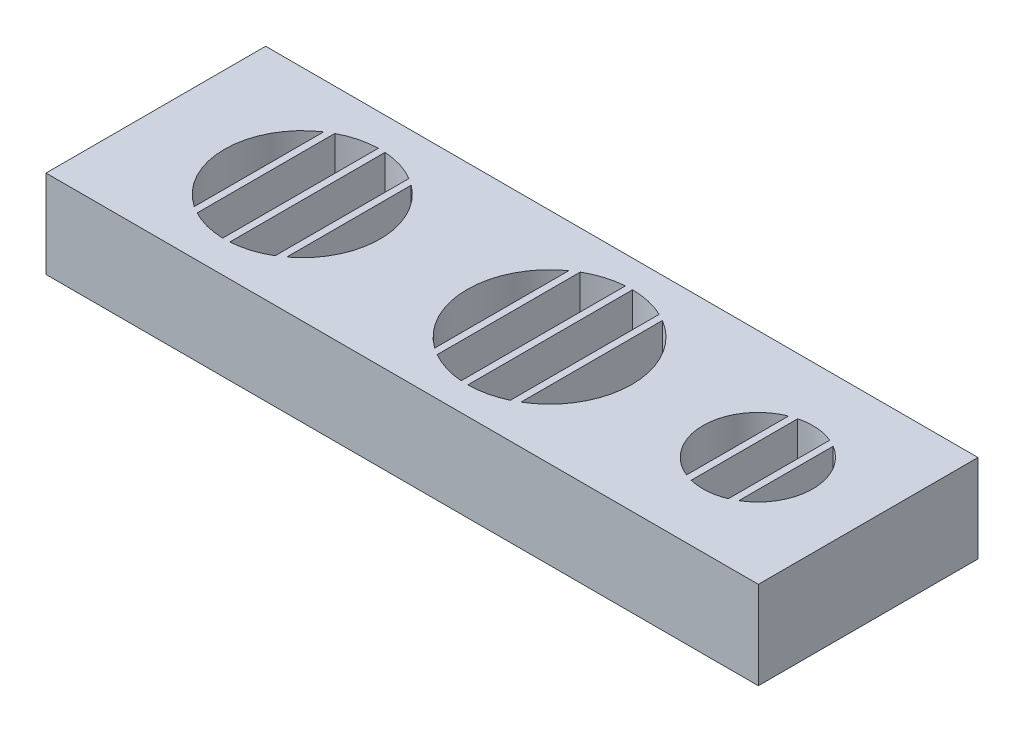
SolidWorks part; units mm, degrees
ref_plane "Front" through (0, 0, 0) normal (0, 0, 1) x (1, 0, 0)
ref_plane "Top" through (0, 0, 0) normal (0, 1, 0) x (1, 0, 0)
ref_plane "Right" through (0, 0, 0) normal (1, 0, 0) x (0, 0, -1)
sketch "Sketch1" plane through (0, 0, 0) normal (0, 1, 0) x (1, 0, 0)
  line L0 (0.8798, 6.35) -> (2.8798, 6.35)
  line L1 (0, 0) -> (38.1, 0)
  line L2 (0, 0) -> (0, 12.7)
  line L3 (0, 12.7) -> (38.1, 12.7)
  line L4 (38.1, 0) -> (38.1, 12.7)
  line L5 (2.8798, 6.35) -> (3.2798, 6.35)
  line L6 (0, 12.7) -> (-3.0858, 12.7)
  line L7 (0, 12.7) -> (0, 0)
  line L8 (0, 0) -> (-3.0858, 0)
  line L9 (-3.0858, 12.7) -> (-3.0858, 0)
  line L10 (3.2798, 6.35) -> (5.2798, 6.35)
  line L11 (5.2798, 6.35) -> (5.6798, 6.35)
  line L12 (5.6798, 6.35) -> (7.6798, 6.35)
  line L13 (7.6798, 6.35) -> (8.0798, 6.35)
  line L14 (8.0798, 6.35) -> (10.0798, 6.35)
  line L15 (2.8798, 10.0917) -> (2.8798, 2.6083)
  line L16 (3.2798, 10.3299) -> (3.2798, 2.3701)
  line L17 (5.2798, 6.35) -> (5.2798, 1.8511)
  line L18 (5.2798, 6.35) -> (5.2798, 10.8489)
  line L19 (5.6798, 6.35) -> (5.6798, 10.84)
  line L20 (5.6798, 6.35) -> (5.6798, 1.86)
  line L21 (7.6798, 6.35) -> (7.6798, 10.2178)
  line L22 (7.6798, 6.35) -> (7.6798, 2.4822)
  line L23 (8.0798, 6.35) -> (8.0798, 9.95)
  line L24 (8.0798, 6.35) -> (8.0798, 2.75)
  line L25 (14.9154, 6.35) -> (16.9154, 6.35)
  line L26 (16.9154, 6.35) -> (17.3154, 6.35)
  line L27 (17.3154, 6.35) -> (19.3154, 6.35)
  line L28 (19.3154, 6.35) -> (19.7154, 6.35)
  line L29 (19.7154, 6.35) -> (21.7154, 6.35)
  line L30 (21.7154, 6.35) -> (22.1154, 6.35)
  line L31 (16.9154, 6.35) -> (16.9154, 10.2294)
  line L32 (17.3154, 6.35) -> (17.3154, 10.4852)
  line L33 (16.9154, 6.35) -> (16.9154, 2.4706)
  line L34 (17.3154, 6.35) -> (17.3154, 2.2148)
  line L35 (19.7154, 6.35) -> (19.7154, 11.1124)
  line L36 (19.3154, 6.35) -> (19.3154, 11.0987)
  line L37 (19.3154, 6.35) -> (19.3154, 1.6013)
  line L38 (19.7154, 6.35) -> (19.7154, 1.5876)
  line L39 (21.7154, 6.35) -> (21.7154, 10.6546)
  line L40 (22.1154, 6.35) -> (22.1154, 10.4415)
  line L41 (21.7154, 6.35) -> (21.7154, 2.0454)
  line L42 (22.1154, 6.35) -> (22.1154, 2.2585)
  line L43 (28.5475, 6.35) -> (30.5475, 6.35)
  line L44 (30.5475, 6.35) -> (30.9475, 6.35)
  line L45 (30.9475, 6.35) -> (32.9475, 6.35)
  line L46 (32.9475, 6.35) -> (33.3475, 6.35)
  line L47 (30.5475, 9.2996) -> (30.5475, 3.4004)
  line L48 (30.9475, 3.271) -> (30.9475, 9.429)
  line L49 (32.9475, 9.2792) -> (32.9475, 3.4208)
  line L50 (33.3475, 9.0776) -> (33.3475, 3.6224)
  circle A0 centre (5.3798, 6.35) radius 4.5
  circle A2 centre (31.7225, 6.35) radius 3.175
  circle A3 centre (19.6779, 6.35) radius 4.7625
  dimension "D1" = 12.7
  dimension "D2" = 38.1
  dimension "D3" = 2
  dimension "D4" = 0.4
  dimension "D5" = 2
  dimension "D6" = 0.4
  dimension "D7" = 2
  dimension "D8" = 0.4
  dimension "D9" = 2
  dimension "D10" = 2
  dimension "D11" = 0.4
  dimension "D12" = 2
  dimension "D13" = 0.4
  dimension "D14" = 2
  dimension "D15" = 0.4
  dimension "D16" = 2
  dimension "D17" = 0.4
  dimension "D18" = 2
  dimension "D19" = 0.4
extrude "Boss-Extrude1" add sketch "Sketch1" along normal blind 5.08 contours L15 A0 L16 L5 | L16 A0 L15 L5 | L19 A0 L18 L11 | L17 A0 L20 L11 | L23 A0 L21 L13 | L22 A0 L24 L13 | L1 L4 L3 L2 A3 A2 A0 | L33 A3 L34 L26 | L37 A3 L38 L28 | L35 A3 L36 L28 | L32 A3 L31 L26 | L40 A3 L39 L30 | L41 A3 L42 L30 | L6 L9 L8 L2 | L48 A2 L47 L44 | L47 A2 L48 L44 | L50 A2 L49 L46 | L49 A2 L50 L46 region at (3.0819, 0, -8.2834) region at (3.0819, 0, -4.4166) region at (5.4798, 0, -8.5987) region at (5.4798, 0, -4.1013) region at (7.8775, 0, -8.2203) region at (7.8775, 0, -4.4797) region at (0.4016, 0, -6.35) region at (-1.5429, 0, -6.35) region at (17.1175, 0, -8.3567) region at (17.1175, 0, -4.3433) region at (19.5155, 0, -8.7292) region at (19.5155, 0, -3.9708) region at (21.9137, 0, -8.4515) region at (21.9137, 0, -4.2485) region at (30.7489, 0, -7.8598) region at (30.7489, 0, -4.8402) region at (33.1451, 0, -7.7677) region at (33.1451, 0, -4.9323)
